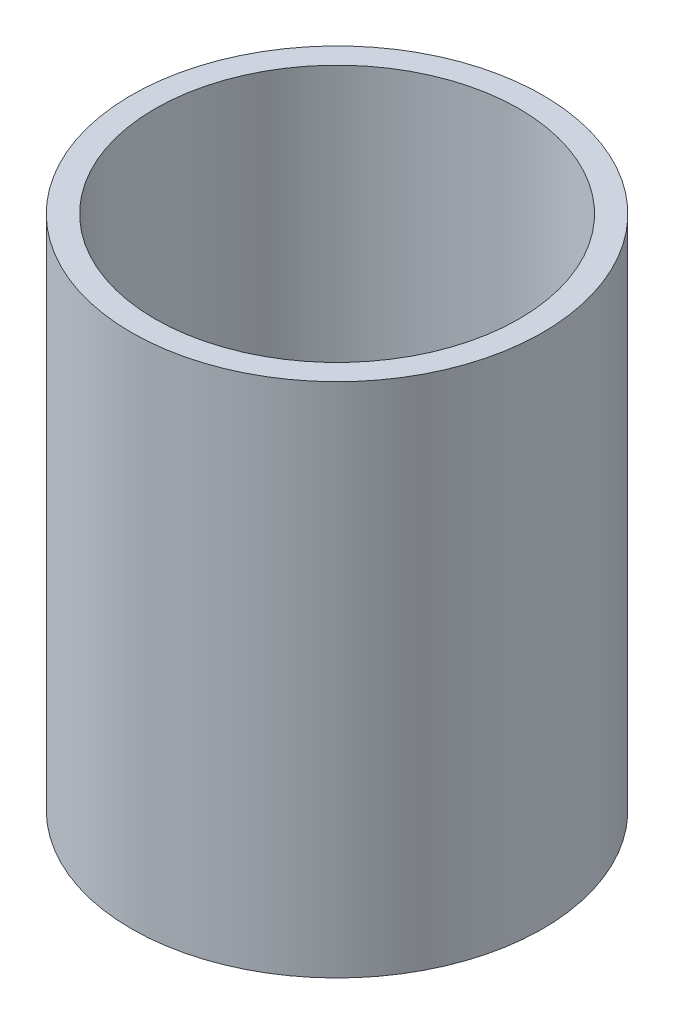
SolidWorks part; units mm, degrees
ref_plane "Front Plane" through (0, 0, 0) normal (0, 0, 1) x (1, 0, 0)
ref_plane "Top Plane" through (0, 0, 0) normal (0, 1, 0) x (1, 0, 0)
ref_plane "Right Plane" through (0, 0, 0) normal (1, 0, 0) x (0, 0, -1)
sketch "Sketch1" plane through (0, 0, 0) normal (0, 1, 0) x (1, 0, 0)
  circle A0 centre (0, 0) radius 55
  dimension "SLEEVE_OD" = 110
extrude "Boss-Extrude1" add sketch "Sketch1" along normal blind 138.1188
sketch "Sketch2" plane through (0, 0, 0) normal (0, 1, 0) x (1, 0, 0)
  circle A0 centre (0, 0) radius 48.6968
  dimension "BORE_D" = 97.3935
extrude "Cut-Extrude1" cut sketch "Sketch2" along normal through all
chamfer "Chamfer1" distance 2.501 angle 57.467 rebuild error yes
